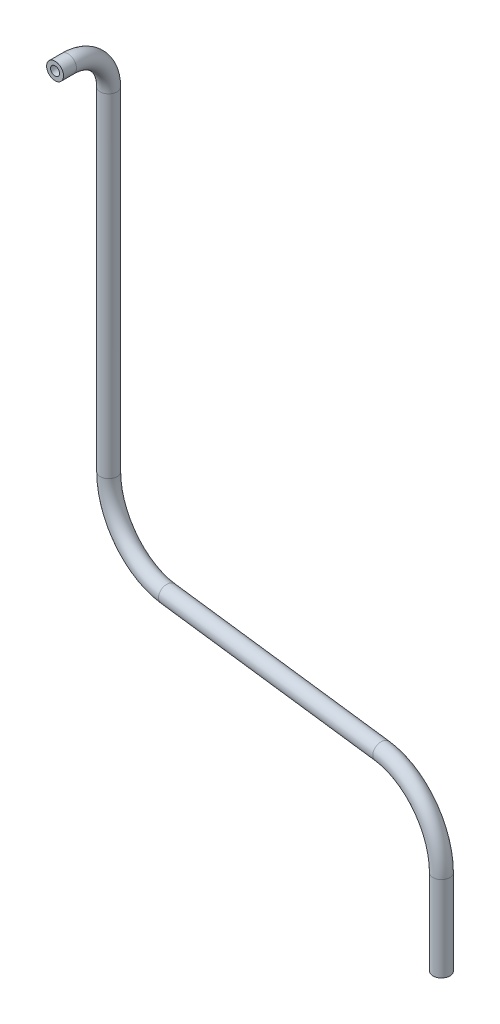
SolidWorks part; units mm, degrees
material "ABS PC"
ref_plane "Front" through (0, 0, 0) normal (0, 0, 1) x (1, 0, 0)
ref_plane "Top" through (0, 0, 0) normal (0, 1, 0) x (1, 0, 0)
ref_plane "Right" through (0, 0, 0) normal (1, 0, 0) x (0, 0, -1)
ref_axis "Axis1" through (0, 0, 55) along (0, 0, -1)
sketch3d "3DSketch1"
  line L0 (-318.4634, 190.2764, 87.147) -> (-318.4634, 190.2764, 82.2897)
  line L1 (-176.7474, -32.6056, 84.047) -> (-176.7474, -0.6673, 84.047)
  line L2 (-318.4634, 175.0364, 67.0497) -> (-318.4634, 50.1327, 67.0497)
  line L3 (-201.9666, 24.7327, 81.0223) -> (-293.2441, 24.7327, 70.0745)
  arc A0 (-318.4634, 50.1327, 67.0497) -> (-293.2441, 24.7327, 70.0745) centre (-293.2441, 50.1327, 70.0745) ccw
  arc A1 (-176.7474, -0.6673, 84.047) -> (-201.9666, 24.7327, 81.0223) centre (-201.9666, -0.6673, 81.0223) ccw
  arc A2 (-318.4634, 175.0364, 67.0497) -> (-318.4634, 190.2764, 82.2897) centre (-318.4634, 175.0364, 82.2897) ccw
  point P7 (-296.2689, 50.1327, 95.2937)
  point P10 (-204.9914, -0.6673, 106.2415)
  point P13 (-303.2234, 175.0364, 82.2897)
  dimension "D1" = 4.8574
ref_plane "Plane1" through (-176.7474, -32.6056, 84.047) normal (0, 1, 0) x (1, 0, 0)
sketch "Sketch1" plane through (-176.7474, -32.6056, 84.047) normal (0, 1, 0) x (1, 0, 0)
  circle A0 centre (0, 0) radius 3.175
  circle A1 centre (0, 0) radius 1.6745
  dimension "D1" = 6.35
  dimension "D2" = 3.349
sweep "Sweep1" add profiles "Sketch1" path "3DSketch1"
